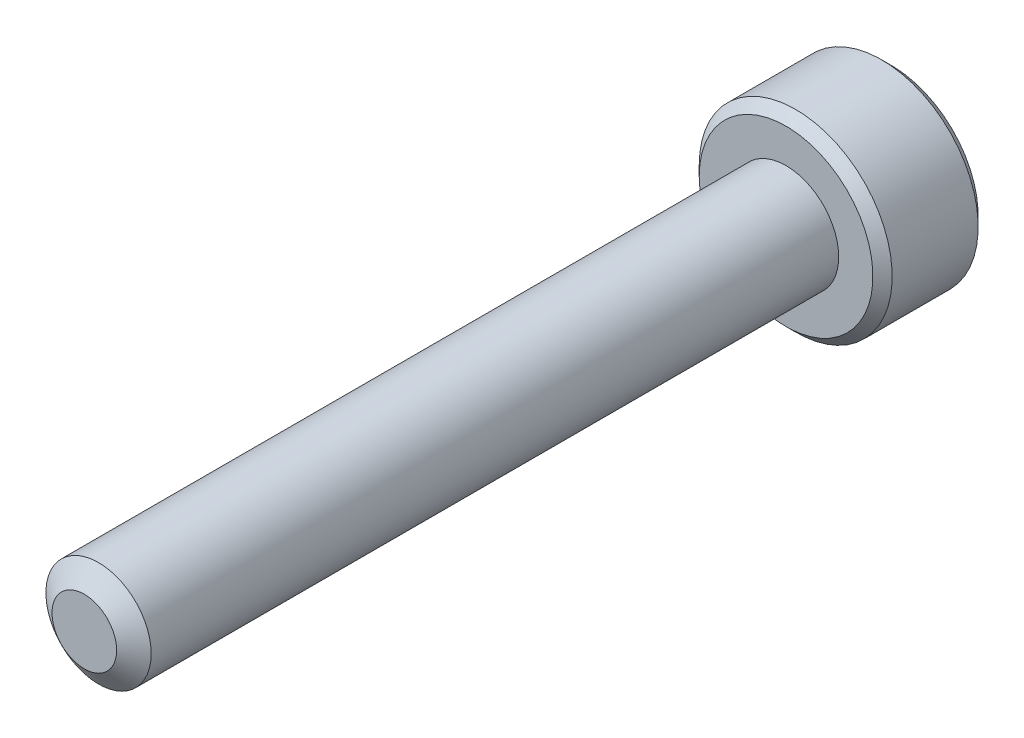
SolidWorks part; units mm, degrees
other "DetailItem1"
ref_plane "Front Plane" through (0, 0, 0) normal (0, 0, 1) x (1, 0, 0)
ref_plane "Top Plane" through (0, 0, 0) normal (0, 1, 0) x (1, 0, 0)
ref_plane "Right Plane" through (0, 0, 0) normal (1, 0, 0) x (0, 0, -1)
sketch "Sketch1" plane through (0, 0, 0) normal (0, 0, 1) x (1, 0, 0)
  circle A0 centre (0, 0) radius 1.5
  dimension "OD" = 3
extrude "Extrude1" add sketch "Sketch1" against normal blind 20
sketch "Sketch2" plane through (0, 0, 0) normal (0, 0, 1) x (1, 0, 0)
  circle A0 centre (0, 0) radius 1.5 construction
  circle A1 centre (0, 0) radius 1.5
curve "Helix/Spiral1" pitch 0.5 height 20.5 turns 41 parameters "pitch"=0.5
sketch "Sketch3" plane through (0, 0, 0) normal (1, 0, 0) x (0, 0, -1)
  line L0 (-0.4375, 1.5) -> (-0.25, 1.1752)
  line L1 (-0.25, 1.1752) -> (-0.1875, 1.1752)
  line L2 (-0.1875, 1.1752) -> (0, 1.5)
  line L3 (-0.4375, 1.5) -> (0, 1.5)
  line L4 (-0.2187, 1.5) -> (-0.2188, 1.1752) construction
  line L5 (-0.3438, 1.3376) -> (-0.0938, 1.3376) construction
  line L6 (0, 1.5) -> (0, -1.5) construction
  dimension "D1" = 0.0625
  dimension "D2" = 0.25
  dimension "D3" = 60
sweep "Cut-Sweep1" [suppressed] cut profiles "Sketch3" path "Helix/Spiral1"
sketch "Sketch4" plane through (0, 0, 0) normal (1, 0, 0) x (0, 0, -1)
  line L0 (0.4053, 1.5) -> (0, 0.9212)
  line L1 (0, 0.9212) -> (0, 1.5)
  line L2 (0.4053, 1.5) -> (0, 1.5)
  line L3 (-0.4375, 1.5) -> (0, 1.5) construction
  line L4 (0, 0) -> (7.0209, 0) construction
  dimension "D1" = 55
  dimension "D2" = 0.254
revolve "Cut-Revolve1" cut sketch "Sketch4" angle 360 about L4
sketch "Sketch6" plane through (0, 0, -20) normal (0, 0, -1) x (-1, 0, 0)
  circle A0 centre (0, 0) radius 2.75
  dimension "head dia" = 5.5
extrude "Extrude2" add sketch "Sketch6" along normal blind 3
sketch "Sketch7" plane through (0, 0, -23) normal (0, 0, -1) x (-1, 0, 0)
  line L1 (0, 1.4434) -> (-1.25, 0.7217)
  line L2 (-1.25, 0.7217) -> (-1.25, -0.7217)
  line L3 (-1.25, -0.7217) -> (0, -1.4434)
  line L4 (0, -1.4434) -> (1.25, -0.7217)
  line L5 (1.25, -0.7217) -> (1.25, 0.7217)
  line L6 (1.25, 0.7217) -> (0, 1.4434)
  circle A0 centre (0, 0) radius 1.25 construction
  dimension "hex dia" = 2.5
extrude "Cut-Extrude1" cut sketch "Sketch7" against normal blind 1.875
sketch "Sketch8" plane through (0, 0, -23) normal (0, 0, -1) x (-1, 0, 0)
  circle A0 centre (0, 0) radius 1.4434
extrude "Cut-Extrude2" cut sketch "Sketch8" against normal through all draft 45
chamfer "Chamfer1" distance 0.275 angle 45 2 edges at (-2.75, 0, -23) (-2.75, 0, -20)
sketch "Sketch10" plane through (0, 0, -20) normal (0, 0, 1) x (1, 0, 0)
  circle A1 centre (0, 0) radius 1.5
  circle A2 centre (0, 0) radius 1.5
  dimension "D1" = 0
ref_plane "Plane1" through (0, 0, 0) normal (0, 0, 1) x (1, 0, 0)
extrude "partial thread" [suppressed] add sketch "Sketch10" along normal up to surface (4 mm away) separate body up to plane "Plane1"
chamfer "Chamfer2" [suppressed] distance 0.06 angle 45
combine bodies "Combine1" [suppressed] operation type add bodies to combine 107 108
sketch "Sketch9" plane through (0, 0, 0) normal (1, 0, 0) x (0, 0, -1)
  line L0 (0, 1.5) -> (0, -1.5) construction
  line L1 (1.25, 1.5) -> (1.25, -1.5) construction
  dimension "D1" = 1.25
equation "\"D3@Helix/Spiral1\" = \"screw length@Extrude1\"+\"pitch@Helix/Spiral1\""
equation "\"D1@Sketch3\" = \"pitch@Helix/Spiral1\"*.125"
equation "\"D2@Sketch3\" = \"pitch@Helix/Spiral1\"*.5"
equation "\"D1@Cut-Extrude1\" = \"hex dia@Sketch7\"*.75"
equation "\"D1@Chamfer1\" = \"head dia@Sketch6\"*.05"
equation "\"D1@Sketch9\" = \"pitch@Helix/Spiral1\"*2.5"
equation "\"D1@Chamfer2\"=\"OD@Sketch1\"*.02"
